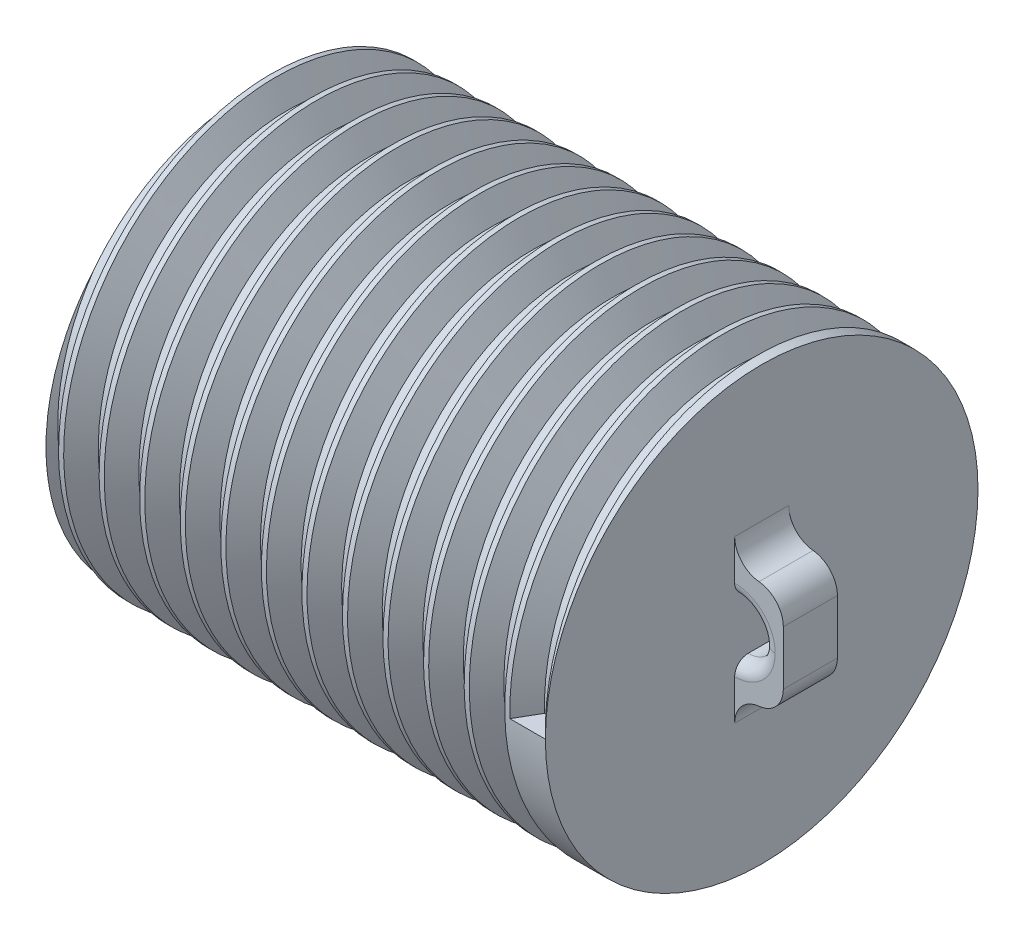
SolidWorks part; units mm, degrees
ref_plane "Front Plane" through (0, 0, 0) normal (0, 0, 1) x (1, 0, 0)
ref_plane "Top Plane" through (0, 0, 0) normal (0, 1, 0) x (1, 0, 0)
ref_plane "Right Plane" through (0, 0, 0) normal (1, 0, 0) x (0, 0, -1)
sketch "Sketch1" plane through (0, 0, 0) normal (1, 0, 0) x (0, 0, -1)
  circle A0 centre (0, 0) radius 8
  dimension "D1" = 16
extrude "Boss-Extrude1" add sketch "Sketch1" along normal blind 19
sketch "Sketch2" plane through (19, 0, 0) normal (1, 0, 0) x (0, 0, -1)
  line L1 (1, 2) -> (-1, 2)
  line L2 (1, 2) -> (1, -2)
  line L3 (1, -2) -> (-1, -2)
  line L4 (-1, 2) -> (-1, -2)
  line L5 (1, 2) -> (-1, -2) construction
  line L6 (1, -2) -> (-1, 2) construction
  point P0 (0, 0)
  dimension "D1" = 2
  dimension "D2" = 4
extrude "Boss-Extrude2" add sketch "Sketch2" along normal blind 1.8
sketch "Sketch3" plane through (0, 0, 1) normal (0, 0, 1) x (1, 0, 0)
  line L0 (19, 2) -> (19, -2) construction
  line L1 (19, 1) -> (20, 1)
  line L2 (19, 1) -> (19, -1)
  line L3 (19, -1) -> (20, -1)
  line L4 (20, 1) -> (20, -1)
  line L5 (20, 1) -> (20, 2) construction
  line L6 (20.8, 2) -> (19, 2) construction
  line L7 (20, -1) -> (20, -2) construction
  line L8 (20.8, -2) -> (19, -2) construction
  dimension "D1" = 1
  dimension "D2" = 2
extrude "Cut-Extrude1" cut sketch "Sketch3" against normal through all
fillet "Fillet1" radius 1 2 edges at (20.8, -2, 0) (20.8, 2, 0)
fillet "Fillet2" radius 1 2 edges at (20, -1, 0) (20, 1, 0)
fillet "Fillet3" radius 0.5 4 edges at (19.7071, -0.7071, -1) (19.7071, 0.7071, -1) (19.7071, -0.7071, 1) (19.7071, 0.7071, 1)
fillet "Fillet4" radius 1 2 edges at (19, 2, 0) (19, -2, 0)
thread "Thread1" pitch 1.5 method cut profile "Thread Profile1" start angle 0, offset 0, length 19, pitch 1.5, diameter 16
ref_plane "Plane1" through (19, 0, 8) normal (0, -1, 0) x (0, 0, 1)
sketch "Thread Profile1" plane through (19, 0, 8) normal (0, -1, 0) x (0, 0, 1)
  line L0 (0, 0) -> (0, 1.5) construction
  line L11 (0, 0) -> (0, 1.3125)
  line L12 (0, 1.3125) -> (-0.8119, 0.8437)
  line L13 (-0.8119, 0.8437) -> (-0.8119, 0.4687)
  line L15 (-0.8119, 0.4687) -> (0, 0)
  line L17 (-0.8119, 0.6562) -> (0, 0.6562) construction
  point P2 (0, 0)
  dimension "Pitch" = 1.5
  dimension "Profile_Angle" = 60
  dimension "Profile_Land" = 0.375
  dimension "Profile_Height" = 0.8119
